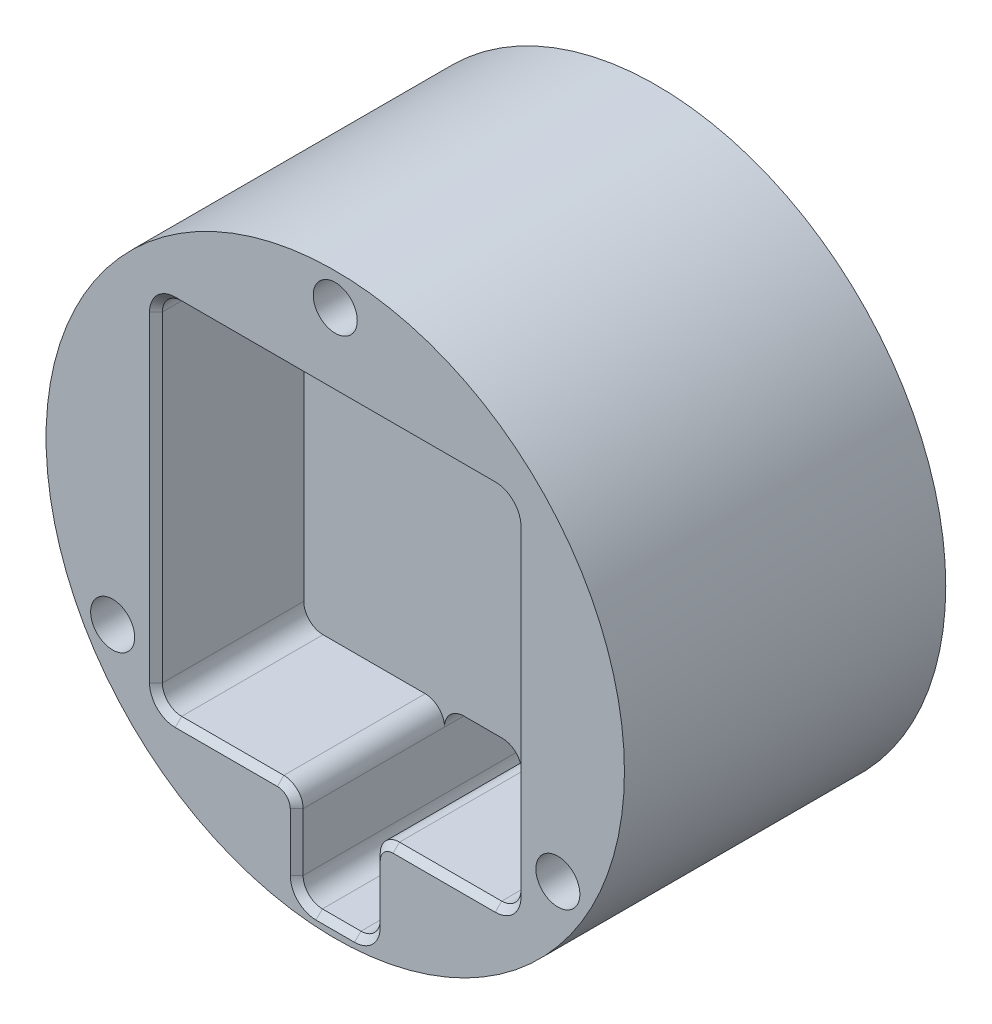
SolidWorks part; units mm, degrees
ref_plane "Plan de face" through (0, 0, 0) normal (0, 0, 1) x (1, 0, 0)
ref_plane "Plan de dessus" through (0, 0, 0) normal (0, 1, 0) x (1, 0, 0)
ref_plane "Plan de droite" through (0, 0, 0) normal (1, 0, 0) x (0, 0, -1)
sketch "Esquisse1" plane through (0, 0, 0) normal (0, 0, 1) x (1, 0, 0)
  circle A0 centre (0, 0) radius 45
  dimension "D1" = 90
extrude "Boss.-Extru.1" add sketch "Esquisse1" along normal blind 50
sketch "Esquisse2" plane through (0, 0, 50) normal (0, 0, 1) x (1, 0, 0)
  line L1 (27.9, -28) -> (-27.9, -28)
  line L2 (27.9, -28) -> (27.9, 28)
  line L3 (27.9, 28) -> (-27.9, 28)
  line L4 (-27.9, -28) -> (-27.9, 28)
  line L5 (27.9, -28) -> (-27.9, 28) construction
  line L6 (27.9, 28) -> (-27.9, -28) construction
  point P0 (0, 0)
  dimension "D1" = 56
  dimension "D2" = 55.8
extrude "Enlèv. mat.-Extru.1" cut sketch "Esquisse2" against normal blind 23
fillet "Congé1" radius 3 4 edges at (27.9, -28, 38.5) (-27.9, -28, 38.5) (-27.9, 28, 38.5) (27.9, 28, 38.5)
sketch "Esquisse3" plane through (0, 0, 50) normal (0, 0, 1) x (1, 0, 0)
  line L0 (-6, -28) -> (-6, -43)
  line L1 (-24.9, -28) -> (24.9, -28) construction
  line L2 (-6, -43) -> (6, -43)
  line L3 (6, -43) -> (6, -28)
  line L4 (6, -28) -> (-6, -28)
  point P5 (0, -28)
  dimension "D1" = 15
  dimension "D2" = 12
extrude "Enlèv. mat.-Extru.2" cut sketch "Esquisse3" against normal through all
fillet "Congé2" radius 3 4 edges at (6, -28, 38.5) (6, -43, 25) (-6, -43, 25) (-6, -28, 38.5)
fillet "Congé3" radius 3 2 edges at (6, -28, 13.5) (-6, -28, 13.5)
chamfer "Chanfrein1" distance 1 angle 45 16 edges at (27.0213, -27.1213, 50) (-27.0213, -27.1213, 50) (27.9, 0, 50) (-27.9, 0, 50) (27.0213, 27.1213, 50) (-27.0213, 27.1213, 50) (0, 28, 50) (5.1213, -42.1213, 50) (6, -35.5, 50) (0, -43, 50) (6.8787, -28.8787, 50) (-5.1213, -42.1213, 50) (16.95, -28, 50) (-6, -35.5, 50) (-6.8787, -28.8787, 50) (-16.95, -28, 50)
sketch "Esquisse5" plane through (0, 0, 50) normal (0, 0, 1) x (1, 0, 0)
  line L0 (0, 40) -> (0, 0) construction
  line L1 (0, 0) -> (-34.641, -20) construction
  circle A0 centre (-34.641, -20) radius 1.6
  circle A1 centre (0, 40) radius 1.6
  circle A2 centre (34.641, -20) radius 1.6
  circle A3 centre (0, 0) radius 40 construction
  point P9 (0, 0)
  dimension "D1" = 3.2
  dimension "D2" = 80
  dimension "D3" = 120
extrude "Enlèv. mat.-Extru.3" cut sketch "Esquisse5" against normal through all
sketch "Esquisse6" plane through (0, 0, 50) normal (0, 0, 1) x (1, 0, 0)
  circle A0 centre (34.641, -20) radius 1.6 construction
  circle A1 centre (0, 40) radius 1.6 construction
  circle A2 centre (-34.641, -20) radius 1.6 construction
  circle A3 centre (34.641, -20) radius 1.6
  circle A4 centre (0, 40) radius 1.6
  circle A5 centre (-34.641, -20) radius 1.6
  circle A6 centre (-34.641, -20) radius 3.425
  circle A7 centre (0, 40) radius 3.425
  circle A8 centre (34.641, -20) radius 3.425
  dimension "D1" = 6.85
extrude "Enlèv. mat.-Extru.4" cut sketch "Esquisse6" against normal blind 5
sketch "Esquisse7" plane through (0, 0, 50) normal (0, 0, 1) x (1, 0, 0)
  circle A0 centre (34.641, -20) radius 1.6 construction
  circle A1 centre (0, 40) radius 1.6 construction
  circle A2 centre (-34.641, -20) radius 1.6 construction
  circle A3 centre (34.641, -20) radius 1.6
  circle A4 centre (0, 40) radius 1.6
  circle A5 centre (-34.641, -20) radius 1.6
  circle A6 centre (-34.641, -20) radius 2.6
  circle A7 centre (0, 40) radius 2.6
  circle A8 centre (34.641, -20) radius 2.6
  dimension "D1" = 5.2
extrude "Enlèv. mat.-Extru.5" cut sketch "Esquisse7" against normal blind 30
chamfer "Chanfrein2" distance 1 angle 45 3 edges at (36.241, -20, 20) (-33.041, -20, 20) (1.6, 40, 20)
sketch "Esquisse8" plane through (0, 0, 0) normal (0, 0, -1) x (-1, 0, 0)
  circle A0 centre (34.641, -20) radius 1.6 construction
  circle A1 centre (0, 40) radius 1.6 construction
  circle A2 centre (-34.641, -20) radius 1.6 construction
  circle A3 centre (34.641, -20) radius 1.6
  circle A4 centre (0, 40) radius 1.6
  circle A5 centre (-34.641, -20) radius 1.6
  circle A6 centre (-34.641, -20) radius 1.925
  circle A7 centre (0, 40) radius 1.925
  circle A8 centre (34.641, -20) radius 1.925
  dimension "D1" = 3.85
  dimension "D2" = 3.85
  dimension "D3" = 3.85
extrude "Enlèv. mat.-Extru.6" cut sketch "Esquisse8" against normal blind 4
